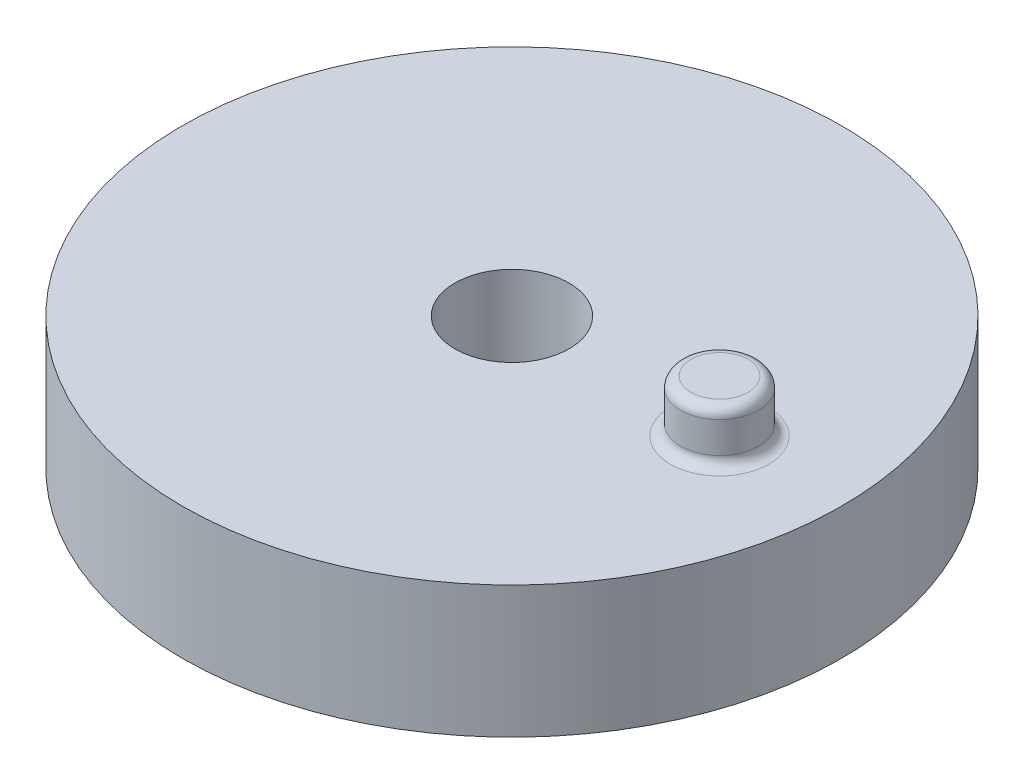
SolidWorks part; units mm, degrees
ref_plane "Front Plane" through (0, 0, 0) normal (0, 0, 1) x (1, 0, 0)
ref_plane "Top Plane" through (0, 0, 0) normal (0, 1, 0) x (1, 0, 0)
ref_plane "Right Plane" through (0, 0, 0) normal (1, 0, 0) x (0, 0, -1)
sketch "Sketch1" plane through (0, 0, 0) normal (0, 1, 0) x (1, 0, 0)
  circle A21 centre (0, 0) radius 63.5
  dimension "D1" = 127
extrude "Boss-Extrude1" add sketch "Sketch1" along normal blind 25.4
sketch "Sketch2" plane through (0, 25.4, 0) normal (0, 1, 0) x (1, 0, 0)
  circle A9 centre (40, 0) radius 7.5
  dimension "D1" = 15
  dimension "D2" = 40
extrude "Boss-Extrude2" add sketch "Sketch2" along normal blind 10
fillet "Fillet1" radius 2 2 edges at (40, 25.4, 7.5) (40, 35.4, 7.5)
sketch "Sketch3" plane through (0, 25.4, 0) normal (0, 1, 0) x (1, 0, 0)
  circle A0 centre (0, 0) radius 11
  dimension "D1" = 22
extrude "Cut-Extrude1" cut sketch "Sketch3" against normal through all
